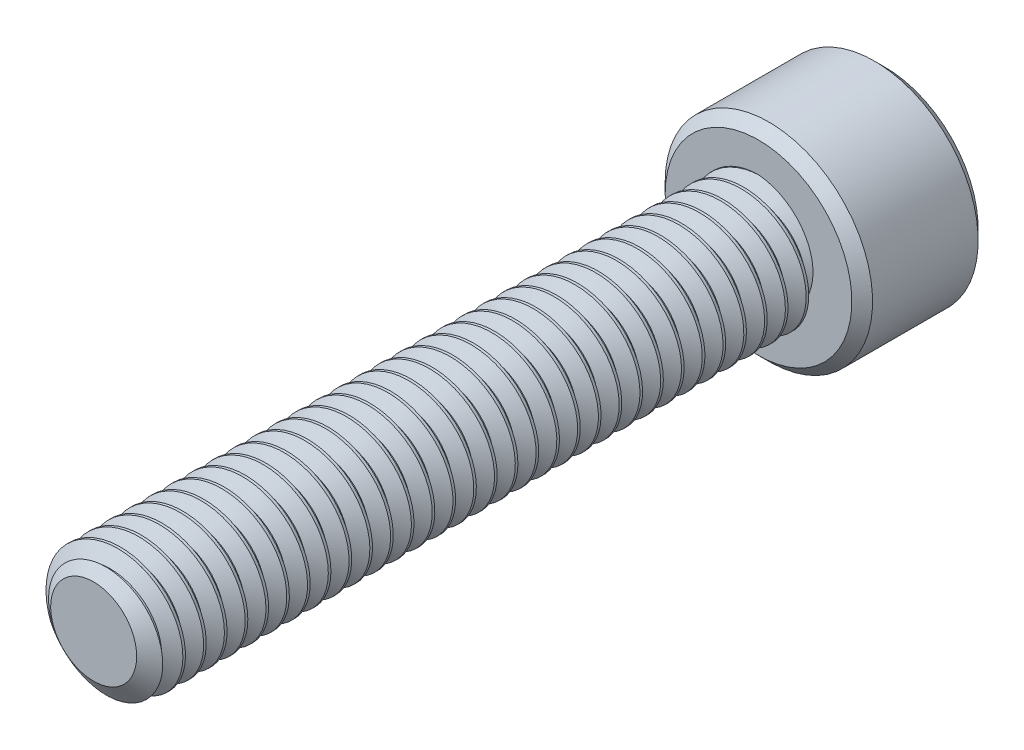
SolidWorks part; units mm, degrees
other "DetailItem1"
ref_plane "Front Plane" through (0, 0, 0) normal (0, 0, 1) x (1, 0, 0)
ref_plane "Top Plane" through (0, 0, 0) normal (0, 1, 0) x (1, 0, 0)
ref_plane "Right Plane" through (0, 0, 0) normal (1, 0, 0) x (0, 0, -1)
sketch "Sketch1" plane through (0, 0, 0) normal (0, 0, 1) x (1, 0, 0)
  circle A0 centre (0, 0) radius 2.413
  dimension "OD" = 4.826
extrude "Extrude1" add sketch "Sketch1" against normal blind 25.4
sketch "Sketch2" plane through (0, 0, 0) normal (0, 0, 1) x (1, 0, 0)
  circle A0 centre (0, 0) radius 2.413 construction
  circle A1 centre (0, 0) radius 2.413
curve "Helix/Spiral1" pitch 0.7937 height 26.1937 turns 33 parameters "pitch"=0.7937
sketch "Sketch3" plane through (0, 0, 0) normal (1, 0, 0) x (0, 0, -1)
  line L0 (-0.6945, 2.413) -> (-0.3969, 1.8974)
  line L1 (-0.3969, 1.8974) -> (-0.2977, 1.8974)
  line L2 (-0.2977, 1.8974) -> (0, 2.413)
  line L3 (-0.6945, 2.413) -> (0, 2.413)
  line L4 (-0.3473, 2.413) -> (-0.3473, 1.8974) construction
  line L5 (-0.5457, 2.1552) -> (-0.1488, 2.1552) construction
  line L6 (0, 2.413) -> (0, -2.413) construction
  dimension "D1" = 0.0992
  dimension "D2" = 0.3969
  dimension "D3" = 60
sweep "Cut-Sweep1" cut profiles "Sketch3" path "Helix/Spiral1"
sketch "Sketch4" plane through (0, 0, 0) normal (1, 0, 0) x (0, 0, -1)
  line L0 (0.5388, 2.413) -> (0, 1.6434)
  line L1 (0, 1.6434) -> (0, 2.413)
  line L2 (0.5388, 2.413) -> (0, 2.413)
  line L3 (-0.6945, 2.413) -> (0, 2.413) construction
  line L4 (0, 0) -> (7.0209, 0) construction
  dimension "D1" = 55
  dimension "D2" = 0.254
revolve "Cut-Revolve1" cut sketch "Sketch4" angle 360 about L4
sketch "Sketch5" plane through (0, 0, 0) normal (1, 0, 0) x (0, 0, -1)
  line L0 (25.4, -1.9083) -> (25.4, 1.7217) construction
  line L1 (25.4, 2.54) -> (0.1202, 2.54)
  line L2 (25.4, 2.54) -> (25.4, 0)
  line L3 (25.4, 0) -> (0, 0)
  line L4 (0, 2.2098) -> (0, 0)
  line L5 (0.1202, 2.54) -> (0, 2.2098)
  line L6 (0, 0) -> (9.9695, 0) construction
  point P3 (0, 2.54)
  point P10 (0, 2.54)
  dimension "D1" = 0.3302
  dimension "D2" = 0.127
  dimension "D3" = 20
  dimension "Min Thread" = 0
revolve "partially thread" [suppressed] add sketch "Sketch5" angle 360 about L6
sketch "Sketch6" plane through (0, 0, -25.4) normal (0, 0, -1) x (-1, 0, 0)
  circle A0 centre (0, 0) radius 3.9624
  dimension "head dia" = 7.9248
extrude "Extrude2" add sketch "Sketch6" along normal blind 4.826
sketch "Sketch7" plane through (0, 0, -30.226) normal (0, 0, -1) x (-1, 0, 0)
  line L1 (0, 2.2914) -> (-1.9844, 1.1457)
  line L2 (-1.9844, 1.1457) -> (-1.9844, -1.1457)
  line L3 (-1.9844, -1.1457) -> (0, -2.2914)
  line L4 (0, -2.2914) -> (1.9844, -1.1457)
  line L5 (1.9844, -1.1457) -> (1.9844, 1.1457)
  line L6 (1.9844, 1.1457) -> (0, 2.2914)
  circle A0 centre (0, 0) radius 1.9844 construction
  dimension "hex dia" = 3.9688
extrude "Cut-Extrude1" cut sketch "Sketch7" against normal blind 2.9766
sketch "Sketch8" plane through (0, 0, -30.226) normal (0, 0, -1) x (-1, 0, 0)
  circle A0 centre (0, 0) radius 2.2914
extrude "Cut-Extrude2" cut sketch "Sketch8" against normal through all draft 45
chamfer "Chamfer1" distance 0.3962 angle 45 2 edges at (-3.9624, 0, -30.226) (-3.9624, 0, -25.4)
sketch "Sketch9" plane through (0, 0, 0) normal (1, 0, 0) x (0, 0, -1)
  line L0 (0, 2.413) -> (0, -2.413) construction
  line L1 (1.9844, 2.413) -> (1.9844, -2.413) construction
  dimension "D1" = 1.9844
equation "\"D3@Helix/Spiral1\" = \"screw length@Extrude1\"+\"pitch@Helix/Spiral1\""
equation "\"D1@Sketch3\" = \"pitch@Helix/Spiral1\"*.125"
equation "\"D2@Sketch3\" = \"pitch@Helix/Spiral1\"*.5"
equation "\"D1@Cut-Extrude1\" = \"hex dia@Sketch7\"*.75"
equation "\"D1@Chamfer1\" = \"head dia@Sketch6\"*.05"
equation "\"D1@Sketch9\" = \"pitch@Helix/Spiral1\"*2.5"
